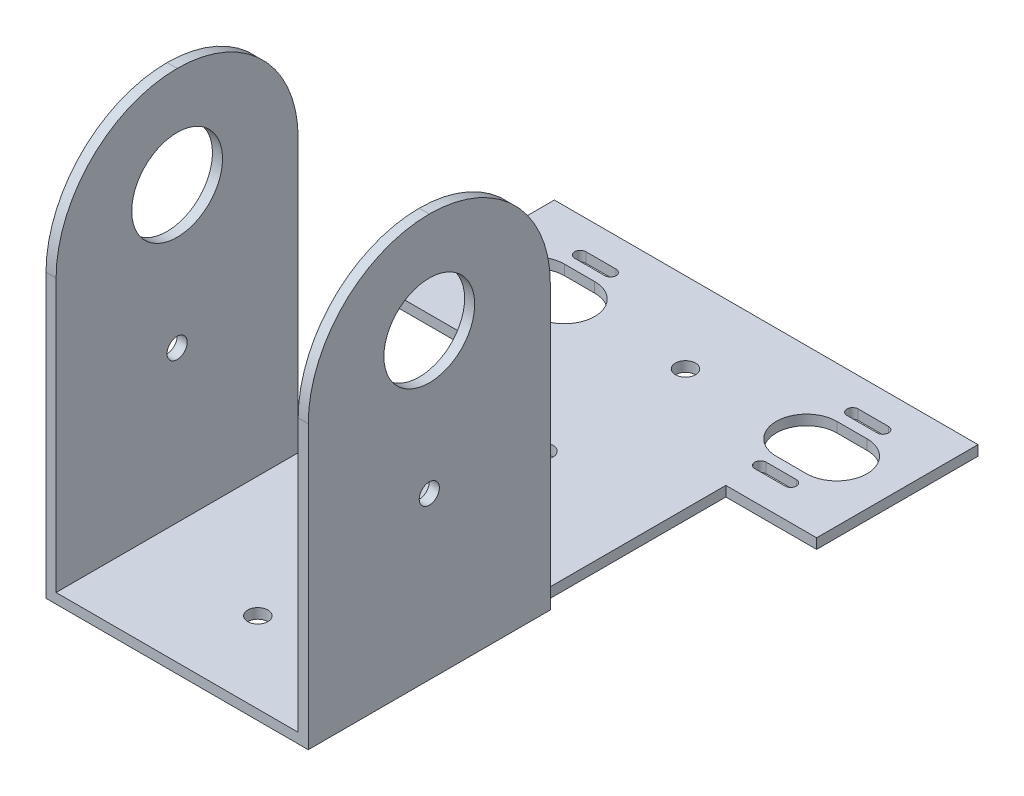
SolidWorks part; units mm, degrees
material "6061-T6 (SS)"
ref_plane "Front Plane" through (0, 0, 0) normal (0, 0, 1) x (1, 0, 0)
ref_plane "Top Plane" through (0, 0, 0) normal (0, 1, 0) x (1, 0, 0)
ref_plane "Right Plane" through (0, 0, 0) normal (1, 0, 0) x (0, 0, -1)
sketch "Sketch1" plane through (0, 0, 0) normal (0, 1, 0) x (1, 0, 0)
  line L1 (-66.675, 25.4) -> (66.675, 25.4)
  line L2 (-66.675, 25.4) -> (-66.675, -25.4)
  line L3 (-66.675, -25.4) -> (66.675, -25.4)
  line L4 (66.675, 25.4) -> (66.675, -25.4)
  line L5 (-66.675, 25.4) -> (66.675, -25.4) construction
  line L6 (-66.675, -25.4) -> (66.675, 25.4) construction
  point P0 (0, 0)
  dimension "D1" = 133.35
  dimension "D2" = 50.8
extrude "Boss-Extrude1" add sketch "Sketch1" along normal blind 3.175
sketch "Sketch2" plane through (0, 3.175, 0) normal (0, 1, 0) x (1, 0, 0)
  line L0 (-47.625, -14.5) -> (-38.1, -14.5) construction
  line L1 (-47.625, -12.722) -> (-38.1, -12.722)
  line L2 (-47.625, -16.278) -> (-38.1, -16.278)
  line L3 (-38.1, 14.5) -> (-47.625, 14.5) construction
  line L4 (-38.1, 12.722) -> (-47.625, 12.722)
  line L5 (-38.1, 16.278) -> (-47.625, 16.278)
  line L7 (-66.675, 25.4) -> (-47.625, 14.5) construction
  line L8 (-47.625, -14.5) -> (-66.675, -25.4) construction
  line L9 (-38.1, 0) -> (-47.625, 0) construction
  line L10 (-38.1, -9.525) -> (-47.625, -9.525)
  line L11 (-38.1, 9.525) -> (-47.625, 9.525)
  line L12 (-66.675, 25.4) -> (-66.675, -25.4) construction
  arc A0 (-47.625, -12.722) -> (-47.625, -16.278) centre (-47.625, -14.5) ccw
  arc A1 (-38.1, -16.278) -> (-38.1, -12.722) centre (-38.1, -14.5) ccw
  arc A2 (-38.1, 12.722) -> (-38.1, 16.278) centre (-38.1, 14.5) ccw
  arc A3 (-47.625, 16.278) -> (-47.625, 12.722) centre (-47.625, 14.5) ccw
  circle A4 centre (-47.625, 14.5) radius 1.65 construction
  arc A5 (-38.1, -9.525) -> (-38.1, 9.525) centre (-38.1, 0) ccw
  arc A6 (-47.625, 9.525) -> (-47.625, -9.525) centre (-47.625, 0) ccw
  point P2 (-42.8625, -14.5)
  point P7 (-42.8625, 14.5)
  point P16 (-47.625, 14.5)
  point P22 (-42.8625, 0)
  point P35 (-57.15, 0)
  point P38 (-66.675, 0)
  dimension "D2" = 9.525
  dimension "D1" = 3.556
  dimension "D3" = 9.525
  dimension "D4" = 19.05
extrude "Cut-Extrude1" cut sketch "Sketch2" against normal blind 3.175
mirror "Mirror1" about plane through (0, 0, 0) normal (1, 0, 0) of "Cut-Extrude1"
sketch "Sketch4" plane through (0, 0, 25.4) normal (0, 0, 1) x (1, 0, 0)
  line L0 (-66.675, 0) -> (66.675, 0) construction
  line L1 (38.1, 3.175) -> (-38.1, 3.175)
  line L2 (38.1, 3.175) -> (38.1, 0)
  line L3 (38.1, 0) -> (-38.1, 0)
  line L4 (-38.1, 3.175) -> (-38.1, 0)
  line L5 (38.1, 3.175) -> (-38.1, 0) construction
  line L6 (38.1, 0) -> (-38.1, 3.175) construction
  line L7 (-66.675, 3.175) -> (0, 1.5875) construction
  line L8 (0, 1.5875) -> (66.675, 3.175) construction
  line L9 (-66.675, 3.175) -> (66.675, 3.175) construction
  point P0 (0, 1.5875)
  dimension "D1" = 76.2
extrude "Boss-Extrude2" add sketch "Sketch4" along normal blind 134.62
sketch "Sketch5" plane through (0, 0, 0) normal (0, -1, 0) x (1, 0, 0)
  line L1 (-38.1, 160.02) -> (-41.275, 160.02)
  line L2 (-38.1, 160.02) -> (-38.1, 83.82)
  line L3 (-38.1, 83.82) -> (-41.275, 83.82)
  line L4 (-41.275, 160.02) -> (-41.275, 83.82)
  line L5 (38.1, 160.02) -> (41.275, 160.02)
  line L6 (38.1, 160.02) -> (38.1, 83.82)
  line L7 (38.1, 83.82) -> (41.275, 83.82)
  line L8 (41.275, 160.02) -> (41.275, 83.82)
  line M11 (38.1, 25.4) -> (38.1, 160.02)
  dimension "D1" = 3.175
  dimension "D2" = 76.2
extrude "Boss-Extrude3" add sketch "Sketch5" against normal blind 127 contours L8 L5 L7 M11 | L4 L3 L2 L1 region at (39.6875, 0, 121.92)
fillet "Fillet1" radius 38.1 4 edges at (39.6875, 127, 160.02) (-39.6875, 127, 160.02) (39.6875, 127, 83.82) (-39.6875, 127, 83.82)
sketch "Sketch6" plane through (-41.275, 0, 0) normal (-1, 0, 0) x (0, 0, 1)
  circle A0 centre (121.92, 95.25) radius 14.2875
  circle A1 centre (121.92, 50.8) radius 3.175
  point P6 (120.348, 50.8278)
  dimension "D1" = 28.575
  dimension "D3" = 6.35
  dimension "D2" = 6.35
  dimension "D4" = 44.45
extrude "Cut-Extrude3" cut sketch "Sketch6" against normal through all
sketch "Sketch3" plane through (0, 3.175, 0) normal (0, 1, 0) x (1, 0, 0)
  line L0 (0, 0) -> (0, -44.8733) construction
  line L1 (0, -44.8733) -> (0, -89.7467) construction
  line L2 (0, -89.7467) -> (0, -134.62) construction
  line L3 (38.1, -160.02) -> (-38.1, -160.02) construction
  circle A0 centre (0, 0) radius 3.175
  circle A1 centre (0, -44.8733) radius 3.175
  circle A2 centre (0, -89.7467) radius 3.175
  circle A3 centre (0, -134.62) radius 3.175
  point P9 (0, -50.9575)
  point P10 (0, -129.7126)
  point P11 (0, -48.6722)
  dimension "D1" = 6.35
  dimension "D2" = 25.4
extrude "Cut-Extrude2" cut sketch "Sketch3" against normal through all
